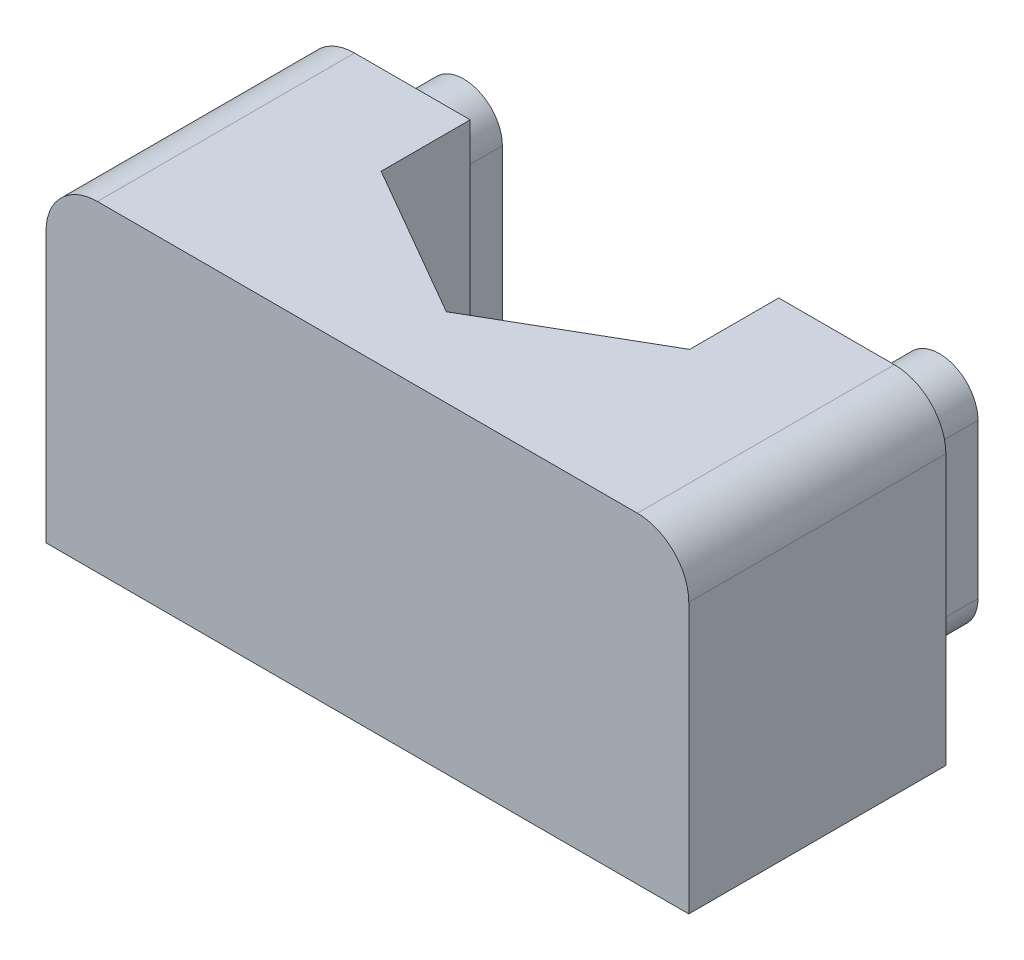
SolidWorks part; units mm, degrees
ref_plane "Plan de face" through (0, 0, 0) normal (0, 0, 1) x (1, 0, 0)
ref_plane "Plan de dessus" through (0, 0, 0) normal (0, 1, 0) x (1, 0, 0)
ref_plane "Plan de droite" through (0, 0, 0) normal (1, 0, 0) x (0, 0, -1)
sketch "Esquisse1" plane through (0, 0, 0) normal (0, 1, 0) x (1, 0, 0)
  line L0 (-3, 21) -> (-3, -21)
  line L5 (-63, 26) -> (-8, 26)
  line L7 (-63, -26) -> (-8, -26)
  line L9 (-63, 26) -> (-8, 26)
  line L10 (-63, 26) -> (-63, 29)
  line L11 (-63, 29) -> (-3, 29)
  line L13 (-63, -26) -> (-8, -26)
  line L14 (-63, -26) -> (-63, -29)
  line L15 (-63, -29) -> (-3, -29)
  line L17 (-3, 29) -> (0, 29)
  line L19 (-3, -29) -> (0, -29)
  line L20 (0, 29) -> (0, -29)
  arc A0 (-8, -26) -> (-3, -21) centre (-8, -21) ccw
  arc A1 (-3, 21) -> (-8, 26) centre (-8, 21) ccw
  point P0 (0, 0)
  point P1 (-3, 0)
  dimension "D9" = 5
  dimension "D1" = 60
  dimension "D2" = 58
  dimension "D3" = 3
  dimension "D4" = 60
  dimension "D5" = 3
  dimension "D6" = 3
  dimension "D7" = 3
  dimension "D8" = 3
extrude "Boss.-Extru.1" add sketch "Esquisse1" along normal blind 12.5 and the other way blind 12.5 contours L20 L17 L11 L10 L5 L0 L7 L14 L15 L19 region at (-3.8589, 0, -25.1411)
sketch "Esquisse3" plane through (0, 0, 0) normal (0, 1, 0) x (1, 0, 0)
  line L1 (-25, 39) -> (0, 39)
  line L2 (-25, 39) -> (-25, 29)
  line L3 (-25, 29) -> (0, 29)
  line L4 (0, 39) -> (0, 29)
  dimension "D1" = 25
  dimension "D2" = 10
extrude "Boss.-Extru.2" add sketch "Esquisse3" against normal blind 12.5
sketch "Esquisse4" plane through (0, 0, 0) normal (0, 1, 0) x (1, 0, 0)
  line L0 (-18.5, 39) -> (-6.5, 44)
  line L1 (-18.5, 35.5359) -> (-18.5, 39)
  line L6 (0, 39) -> (-25, 39) construction
  line L7 (-18.5, 35.5359) -> (-12.5, 32.0718)
  line L12 (-12.5, 32.0718) -> (-6.5, 35.5359)
  line L13 (-18.5, 35.5359) -> (-18.5, 42.4641) construction
  line L14 (-18.5, 42.4641) -> (-12.5, 45.9282) construction
  line L15 (-12.5, 45.9282) -> (-6.5, 42.4641) construction
  line L16 (-6.5, 42.4641) -> (-6.5, 35.5359) construction
  line L17 (-6.5, 35.5359) -> (-6.5, 44)
  point P0 (-18.5, 39)
  point P8 (-12.5, 39)
  dimension "D1" = 120
  dimension "D2" = 120
  dimension "D3" = 12
extrude "Enlèv. mat.-Extru.3" cut sketch "Esquisse4" against normal blind 7.5
sketch "Esquisse5" plane through (0, -7.5, 0) normal (0, 1, 0) x (1, 0, 0)
  line L0 (-6.5, 39) -> (-18.5, 39) construction
  circle A0 centre (-12.5, 39) radius 5
  dimension "D1" = 10
extrude "Enlèv. mat.-Extru.4" cut sketch "Esquisse5" against normal through all
sketch "Esquisse6" plane through (0, 12.5, 0) normal (0, 1, 0) x (1, 0, 0)
  line L1 (-63, 29) -> (10.8419, 29)
  line L2 (-63, 29) -> (-63, -33.7818)
  line L3 (-63, -33.7818) -> (10.8419, -33.7818)
  line L4 (10.8419, 29) -> (10.8419, -33.7818)
extrude "Enlèv. mat.-Extru.5" cut sketch "Esquisse6" against normal through all
sketch "Esquisse7" plane through (0, 0, -39) normal (0, 0, -1) x (-1, 0, 0)
  line L0 (3.25, -3.25) -> (3.25, -9.25) construction
  line L1 (4.75, -3.25) -> (4.75, -9.25)
  line L2 (1.75, -3.25) -> (1.75, -9.25)
  line L3 (3.25, 0) -> (3.25, -12.5) construction
  line L4 (0, 0) -> (6.5, 0) construction
  line L5 (0, -12.5) -> (7.5, -12.5) construction
  line L6 (12.5, -7.5) -> (12.5, 0) construction
  line L7 (21.75, -3.25) -> (21.75, -9.25) construction
  line L8 (20.25, -3.25) -> (20.25, -9.25)
  line L9 (23.25, -3.25) -> (23.25, -9.25)
  arc A0 (4.75, -3.25) -> (1.75, -3.25) centre (3.25, -3.25) ccw
  arc A1 (1.75, -9.25) -> (4.75, -9.25) centre (3.25, -9.25) ccw
  arc A2 (20.25, -3.25) -> (23.25, -3.25) centre (21.75, -3.25) cw
  arc A3 (23.25, -9.25) -> (20.25, -9.25) centre (21.75, -9.25) cw
  point P2 (3.25, -6.25)
  point P14 (3.25, -6.25)
  point P19 (21.75, -6.25)
  dimension "D1" = 1.5
  dimension "D2" = 6
extrude "Boss.-Extru.3" add sketch "Esquisse7" along normal blind 3
fillet "Congé1" radius 2 2 edges at (0, 0, -34) (-25, 0, -34)
